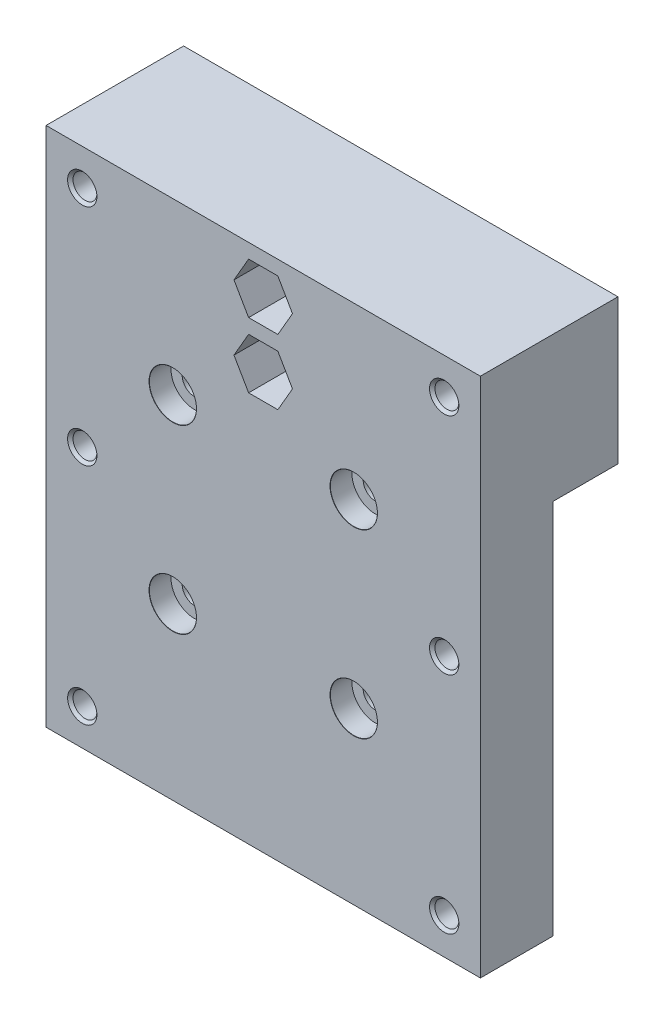
SolidWorks part; units mm, degrees
ref_plane "Front Plane" through (0, 0, 0) normal (0, 0, 1) x (1, 0, 0)
ref_plane "Top Plane" through (0, 0, 0) normal (0, 1, 0) x (1, 0, 0)
ref_plane "Right Plane" through (0, 0, 0) normal (1, 0, 0) x (0, 0, -1)
sketch "Sketch1" plane through (0, 0, 0) normal (0, 0, 1) x (1, 0, 0)
  line L1 (-12.5, 12.5) -> (12.5, 12.5)
  line L2 (-12.5, 12.5) -> (-12.5, -12.5)
  line L3 (-12.5, -12.5) -> (12.5, -12.5)
  line L4 (12.5, 12.5) -> (12.5, -12.5)
  line L5 (-12.5, 12.5) -> (12.5, -12.5) construction
  line L6 (-12.5, -12.5) -> (12.5, 12.5) construction
  line L7 (-30, 36) -> (30, 36)
  line L8 (-30, 36) -> (-30, -36)
  line L9 (-30, -36) -> (30, -36)
  line L10 (30, 36) -> (30, -36)
  line L11 (-30, 36) -> (30, -36) construction
  line L12 (-30, -36) -> (30, 36) construction
  line L13 (-30, -10) -> (30, -10)
  line L14 (-30, -10) -> (-30, 10)
  line L15 (-30, 10) -> (30, 10)
  line L16 (30, -10) -> (30, 10)
  line L17 (-30, -10) -> (30, 10) construction
  line L18 (-30, 10) -> (30, -10) construction
  line L19 (-30, -16) -> (30, -16)
  line L20 (-30, -16) -> (-30, 16)
  line L21 (-30, 16) -> (30, 16)
  line L22 (30, -16) -> (30, 16)
  line L23 (-30, -16) -> (30, 16) construction
  line L24 (-30, 16) -> (30, -16) construction
  point P0 (0, 0)
  point P6 (0, 0)
  point P11 (0, 0)
  point P16 (0, 0)
  dimension "D1" = 25
  dimension "D2" = 25
  dimension "D3" = 60
  dimension "D4" = 20
  dimension "D5" = 20
  dimension "D6" = 32
sketch "Sketch2" plane through (0, 0, 0) normal (0, 0, 1) x (1, 0, 0)
  line L0 (-30, -36) -> (30, -36) construction
  line L1 (-30, 36) -> (-30, -36) construction
  line L2 (-30, 36) -> (30, 36) construction
  line L3 (30, 36) -> (30, -36) construction
  line L4 (-30, -36) -> (30, -36)
  line L5 (-30, 36) -> (-30, -36)
  line L6 (-30, 36) -> (30, 36)
  line L7 (30, 36) -> (30, -36)
extrude "Boss-Extrude1" add sketch "Sketch2" along normal blind 10
sketch "Sketch9" plane through (0, 0, 0) normal (0, 0, -1) x (-1, 0, 0)
  line L0 (30, 36) -> (30, -36) construction
  line L1 (-30, 36) -> (30, 36)
  line L2 (-30, 36) -> (-30, 16)
  line L3 (-30, 16) -> (30, 16)
  line L4 (30, 36) -> (30, 16)
  dimension "D1" = 16
extrude "Boss-Extrude2" add sketch "Sketch9" along normal blind 9
hole_wizard "CBORE for M3 SHCS1" positions "Sketch5" profile "Sketch6" counterbore size "M3" standard "ANSI Metric"
sketch "Sketch5" plane through (0, 0, 10) normal (0, 0, 1) x (1, 0, 0)
  point P0 (-12.5, 12.5)
  point P2 (12.5, 12.5)
  point P4 (12.5, -12.5)
  point P6 (-12.5, -12.5)
  point P10 (0, 0)
  point P12 (0, 0)
  point P14 (0, 0)
  point P16 (0, 0)
sketch "Sketch6" plane through (-12.5, 12.5, 10) normal (1, 0, 0) x (0, -1, 0)
  line L0 (0, 0) -> (0, 11.0215)
  line L1 (0, 11.0215) -> (1.7, 10)
  line L2 (1.7, 10) -> (1.7, 3)
  line L3 (1.7, 3) -> (3.25, 3)
  line L5 (3.25, 3) -> (3.25, 0.025)
  line L6 (3.25, 0.025) -> (3.275, 0)
  line L7 (3.275, 0) -> (0, 0)
  line L8 (-3.25, 0.025) -> (-3.275, 0) construction
  line L10 (0, 11.0215) -> (-1.7, 10) construction
  line L11 (0, -6.35) -> (0, 107.95) construction
  dimension "Hole Dia." = 3.4
  dimension "Hole Depth" = 10
  dimension "C'Bore Dia." = 6.5
  dimension "C'Bore Depth" = 3
  dimension "Near C'Sink Dia." = 6.55
  dimension "Near C'Sink Angle" = 90
  dimension "Drill Angle" = 118
sketch "Sketch7" plane through (0, 0, 10) normal (0, 0, 1) x (1, 0, 0)
  line L1 (-30, 30.5) -> (30, 30.5) construction
  line L2 (-30, 36) -> (-30, -36) construction
  line L3 (30, -36) -> (30, 36) construction
  line L4 (30, 36) -> (-30, 36) construction
  line L5 (-30, 21.5) -> (30, 21.5) construction
  line L6 (-30, 16) -> (30, 16) construction
  line L8 (4.0415, 21.5) -> (2.0207, 25)
  line L9 (2.0207, 25) -> (-2.0207, 25)
  line L10 (-2.0207, 25) -> (-4.0415, 21.5)
  line L11 (-4.0415, 21.5) -> (-2.0207, 18)
  line L12 (-2.0207, 18) -> (2.0207, 18)
  line L13 (2.0207, 18) -> (4.0415, 21.5)
  line L14 (4.0415, 30.5) -> (2.0207, 34)
  line L15 (2.0207, 34) -> (-2.0207, 34)
  line L16 (-2.0207, 34) -> (-4.0415, 30.5)
  line L17 (-4.0415, 30.5) -> (-2.0207, 27)
  line L18 (-2.0207, 27) -> (2.0207, 27)
  line L19 (2.0207, 27) -> (4.0415, 30.5)
  circle A0 centre (0, 21.5) radius 3.5 construction
  circle A1 centre (0, 30.5) radius 3.5 construction
  point P21 (4.0415, 21.5)
  point P29 (4.0415, 30.5)
  dimension "D1" = 5.5
  dimension "D2" = 5.5
  dimension "D3" = 7
  dimension "D4" = 7
extrude "Cut-Extrude1" cut sketch "Sketch7" against normal blind 11
sketch "Sketch8" plane through (0, 0, -1) normal (0, 0, 1) x (1, 0, 0)
  line L0 (-4.0415, 21.5) -> (4.0415, 21.5) construction
  line L1 (4.0415, 30.5) -> (-4.0415, 30.5) construction
  circle A0 centre (0, 30.5) radius 2.1
  circle A1 centre (0, 21.5) radius 2.1
  dimension "D1" = 4.2
extrude "Cut-Extrude2" cut sketch "Sketch8" against normal through all
sketch "Sketch10" plane through (0, 0, 10) normal (0, 0, 1) x (1, 0, 0)
  line L0 (-30, -36) -> (30, -36) construction
  line L1 (-25, 31) -> (25, 31)
  line L2 (-25, 31) -> (-25, -31)
  line L3 (-25, -31) -> (25, -31)
  line L4 (25, 31) -> (25, -31)
  line L5 (-25, 31) -> (25, -31) construction
  line L6 (-25, -31) -> (25, 31) construction
  line L7 (30, -36) -> (30, 36) construction
  point P0 (0, 0)
  point P10 (0, 0)
  dimension "D1" = 5
  dimension "D2" = 5
hole_wizard "M4x0.7 Tapped Hole1" positions "Sketch11" profile "Sketch12" tap size "M4x0.7" standard "ANSI Metric" end condition through all
sketch "Sketch11" plane through (0, 0, 10) normal (0, 0, 1) x (1, 0, 0)
  point P0 (-25, 31)
  point P3 (-25, -31)
  point P6 (25, -31)
  point P9 (25, 31)
  point P12 (-25, 0)
  point P14 (25, 0)
  point P17 (25, 0)
  point P18 (0, 0)
  point P20 (25, 0)
  point P21 (0, 0)
  point P22 (0, 0)
  point P23 (0, 0)
  point P24 (-25, 0)
sketch "Sketch12" plane through (-25, 31, 10) normal (1, 0, 0) x (0, -1, 0)
  line L0 (0, 0) -> (0, 19)
  line L1 (0, 19) -> (1.65, 19)
  line L2 (1.65, 19) -> (1.65, 0.375)
  line L3 (1.65, 0.375) -> (2.025, 0)
  line L5 (2.025, 0) -> (0, 0)
  line L6 (-1.65, 0.375) -> (-2.025, 0) construction
  line L11 (0, -6.35) -> (0, 107.95) construction
  dimension "Thru Tap Drill Dia." = 3.3
  dimension "Thru Tap Drill Depth" = 19
  dimension "Near C'Sink Dia." = 4.05
  dimension "Near C'Sink Angle" = 90
cosmetic thread "Hole Thread1" parameters "D2"=4
cosmetic thread "Hole Thread2" parameters "D2"=4
cosmetic thread "Hole Thread3" parameters "D2"=4
cosmetic thread "Hole Thread4" parameters "D2"=4
cosmetic thread "Hole Thread5" parameters "D2"=4
cosmetic thread "Hole Thread6" parameters "D2"=4
